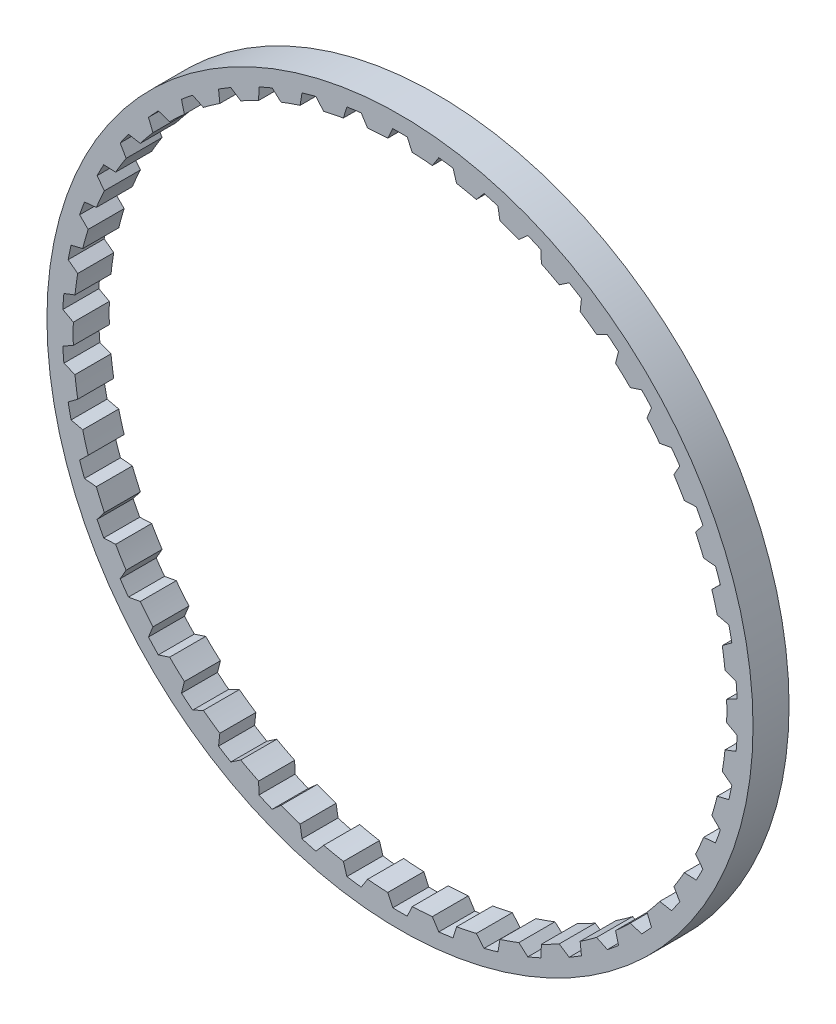
SolidWorks part; units mm, degrees
other "Marquage1"
sketch "Esquisse3" plane through (55, 55, 15) normal (0.7187, 0.1043, 0.6874) x (0.6932, -0.0306, -0.7201)
other "Marquage2"
sketch "Esquisse4" plane through (96.5, 96.5, -15) normal (0.7752, 0.2567, -0.5772) x (-0.5535, -0.1644, -0.8165)
ref_plane "Plan de face" through (0, 0, 0) normal (0, 0, 1) x (1, 0, 0)
ref_plane "Plan de dessus" through (0, 0, 0) normal (0, 1, 0) x (1, 0, 0)
ref_plane "Plan de droite" through (0, 0, 0) normal (1, 0, 0) x (0, 0, -1)
sketch "Esquisse2" plane through (0, 0, 0) normal (1, 0, 0) x (0, 0, -1)
  line L1 (5, 88) -> (-5, 88)
  line L2 (5, 88) -> (5, 98)
  line L3 (5, 98) -> (-5, 98)
  line L4 (-5, 88) -> (-5, 98)
  line L5 (5, 88) -> (-5, 98) construction
  line L6 (5, 98) -> (-5, 88) construction
  line L13 (-7.6364, 0) -> (7.6364, 0) construction
  point P0 (0, 93)
  dimension "D1" = 10
  dimension "D2" = 196
  dimension "D5" = 10
revolve "Révolution1" add sketch "Esquisse2" angle 360 about L13
sketch "Esquisse5" plane through (0, 0, 0) normal (0, 0, 1) x (1, 0, 0)
  line L0 (-6.25, 90.5045) -> (0, 0)
  line L1 (0, 0) -> (6.25, 90.5045)
  line L2 (0, 0) -> (0, 145.9894) construction
  line L3 (-1.1173, 16.18) -> (1.1173, 16.18) construction
  line L5 (-2, 93.6563) -> (-3.3989, 90.6563)
  line L7 (2, 93.6563) -> (3.3989, 90.6563)
  line L8 (-2, 93.6563) -> (3.3989, 90.6563) construction
  line L9 (-3.3989, 90.6563) -> (2, 93.6563) construction
  arc A0 (6.25, 90.5045) -> (3.3989, 90.6563) centre (0, 0) ccw
  arc A1 (-3.3989, 90.6563) -> (-6.25, 90.5045) centre (0, 0) ccw
  arc A2 (2, 93.6563) -> (-2, 93.6563) centre (0, 0) ccw
  point P4 (0, 92.545)
  dimension "D1" = 90.72
  dimension "D5" = 25
  dimension "D2" = 12.5
  dimension "D3" = 3
  dimension "D4" = 4
  dimension "D6" = 16.18
  dimension "D7" = 7.901
extrude "Enlèv. mat.-Extru.1" cut sketch "Esquisse5" against normal through all both and the other way through all
ref_axis "Axe1" through (0, 0, -5) along (0, 0, 1)
pattern_circular "Répétition circulaire1" count 46 over 360 about axis through (0, 0, -5) along (0, 0, 1) of "Enlèv. mat.-Extru.1"
